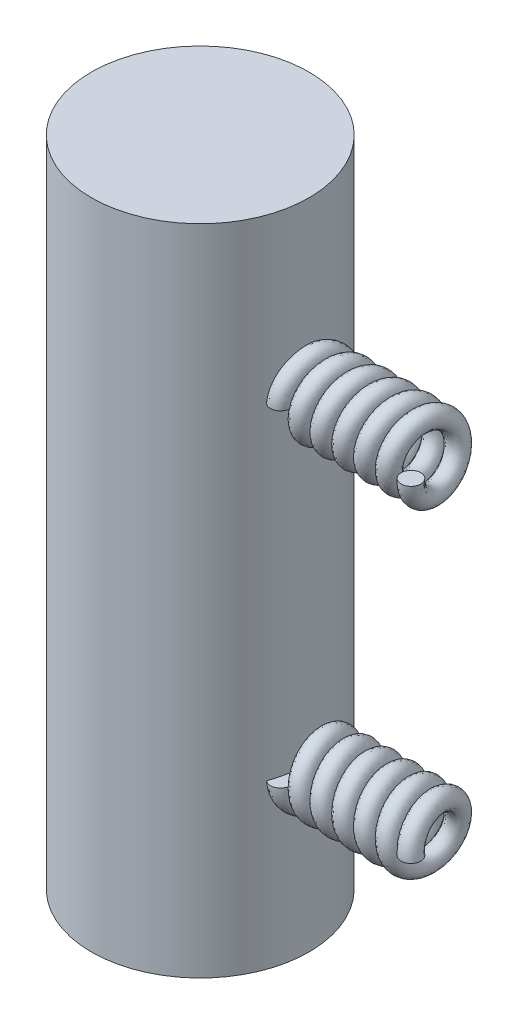
SolidWorks part; units mm, degrees
ref_plane "Front Plane" through (0, 0, 0) normal (0, 0, 1) x (1, 0, 0)
ref_plane "Top Plane" through (0, 0, 0) normal (0, 1, 0) x (1, 0, 0)
ref_plane "Right Plane" through (0, 0, 0) normal (1, 0, 0) x (0, 0, -1)
sketch "Sketch1" plane through (0, 0, 0) normal (0, 1, 0) x (1, 0, 0)
  circle A0 centre (0, 0) radius 5
  dimension "D1" = 10
extrude "Boss-Extrude1" add sketch "Sketch1" along normal mid plane 30
ref_plane "Plane1" through (5, 0, 0) normal (1, 0, 0) x (0, 0, -1)
sketch "Sketch3" plane through (5, 0, 0) normal (1, 0, 0) x (0, 0, -1)
  circle A0 centre (0, 7.5) radius 1.3213
  dimension "D1" = 7.5
curve "Helix/Spiral1" pitch 1 height 6 radius 1.3213 left hand yes centre (5, 7.5, 0) axis (1, 0, 0) start towards (0, 0, 1)
ref_plane "Plane2" through (0, 7.5, 0) normal (0, 1, 0) x (1, 0, 0)
sketch "Sketch4" plane through (0, 7.5, 0) normal (0, 1, 0) x (1, 0, 0)
  line L0 (5, -5.5) -> (5, 5.5) construction
  circle A0 centre (5, -1.3213) radius 0.45
  spline S0 degree 3 poles (5, -1.3213) (5.0207, -1.3213) (5.0626, -1.2525) (5.125, -0.9586) (5.1875, -0.5188) (5.25, 0) (5.3125, 0.5188) (5.375, 0.9586) (5.4375, 1.2525) (5.5, 1.3557) (5.5625, 1.2525) (5.625, 0.9586) (5.7083, 0.3722) (5.7917, -0.3722) (5.875, -0.9586) (5.9375, -1.2525) (6, -1.3557) (6.0625, -1.2525) (6.125, -0.9586) (6.2083, -0.3722) (6.2917, 0.3722) (6.375, 0.9586) (6.4375, 1.2525) (6.5, 1.3557) (6.5625, 1.2525) (6.625, 0.9586) (6.7083, 0.3722) (6.7917, -0.3722) (6.875, -0.9586) (6.9375, -1.2525) (7, -1.3557) (7.0625, -1.2525) (7.125, -0.9586) (7.2083, -0.3722) (7.2917, 0.3722) (7.375, 0.9586) (7.4375, 1.2525) (7.5, 1.3557) (7.5625, 1.2525) (7.625, 0.9586) (7.7083, 0.3722) (7.7917, -0.3722) (7.875, -0.9586) (7.9375, -1.2525) (8, -1.3557) (8.0625, -1.2525) (8.125, -0.9586) (8.2083, -0.3722) (8.2917, 0.3722) (8.375, 0.9586) (8.4375, 1.2525) (8.5, 1.3557) (8.5625, 1.2525) (8.625, 0.9586) (8.7083, 0.3722) (8.7917, -0.3722) (8.875, -0.9586) (8.9375, -1.2525) (9, -1.3557) (9.0625, -1.2525) (9.125, -0.9586) (9.2083, -0.3722) (9.2917, 0.3722) (9.375, 0.9586) (9.4375, 1.2525) (9.5, 1.3557) (9.5625, 1.2525) (9.625, 0.9586) (9.7083, 0.3722) (9.7917, -0.3722) (9.875, -0.9586) (9.9375, -1.2525) (10, -1.3557) (10.0625, -1.2525) (10.125, -0.9586) (10.2083, -0.3722) (10.2917, 0.3722) (10.375, 0.9586) (10.4375, 1.2525) (10.5, 1.3557) (10.5625, 1.2525) (10.625, 0.9586) (10.6875, 0.5188) (10.75, 0) (10.8125, -0.5188) (10.875, -0.9586) (10.9374, -1.2525) (10.9793, -1.3213) (11, -1.3213) knots 0 0 0 0 0.010417 0.020833 0.03125 0.041667 0.052083 0.0625 0.072917 0.083333 0.09375 0.104167 0.114583 0.135417 0.145833 0.15625 0.166667 0.177083 0.1875 0.197917 0.21875 0.229167 0.239583 0.25 0.260417 0.270833 0.28125 0.302083 0.3125 0.322917 0.333333 0.34375 0.354167 0.364583 0.385417 0.395833 0.40625 0.416667 0.427083 0.4375 0.447917 0.46875 0.479167 0.489583 0.5 0.510417 0.520833 0.53125 0.552083 0.5625 0.572917 0.583333 0.59375 0.604167 0.614583 0.635417 0.645833 0.65625 0.666667 0.677083 0.6875 0.697917 0.71875 0.729167 0.739583 0.75 0.760417 0.770833 0.78125 0.802083 0.8125 0.822917 0.833333 0.84375 0.854167 0.864583 0.885417 0.895833 0.90625 0.916667 0.927083 0.9375 0.947917 0.958333 0.96875 0.979167 0.989583 1 1 1 1 construction
sweep "Sweep1" add profiles "Sketch4" path "Helix/Spiral1"
mirror "Mirror1" about plane through (0, 0, 0) normal (0, 1, 0) of "Sweep1"
